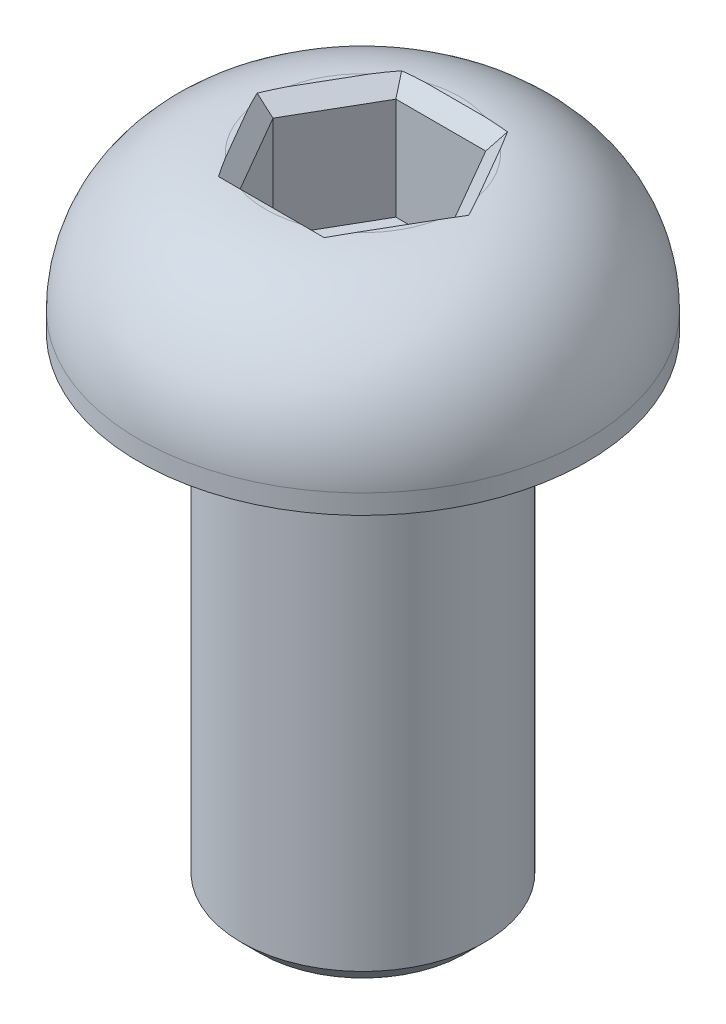
SolidWorks part; units mm, degrees
material "AISI 304"
ref_plane "Front Plane" through (0, 0, 0) normal (0, 0, 1) x (1, 0, 0)
ref_plane "Top Plane" through (0, 0, 0) normal (0, 1, 0) x (1, 0, 0)
ref_plane "Right Plane" through (0, 0, 0) normal (1, 0, 0) x (0, 0, -1)
sketch "Sketch1" plane through (0, 0, 0) normal (0, 0, 1) x (1, 0, 0)
  line L0 (0, 16.7549) -> (-2.54, 16.7549)
  line L1 (-5.842, 13.208) -> (-5.842, 12.7)
  line L2 (-5.842, 12.7) -> (-3.175, 12.7)
  line L3 (-3.175, 12.7) -> (-3.175, 0)
  line L4 (0, 16.7549) -> (0, 0)
  line L5 (-3.175, 0) -> (0, 0)
  line L16 (0, 0) -> (0, 19.0681) construction
  arc A0 (-2.54, 16.7549) -> (-5.842, 13.208) centre (-2.286, 13.208) ccw
  dimension "D1" = 3.556
  dimension "D2" = 4.572
  dimension "D3" = 0.508
  dimension "D4" = 0.508
  dimension "D5" = 11.684
  dimension "D6" = 6.35
  dimension "D7" = 16.7549
  dimension "D8" = 2.54
revolve "Revolve1" add sketch "Sketch1" angle 360 about L16
sketch "Sketch2" plane through (0, 16.7549, 0) normal (0, 1, 0) x (1, 0, 0)
  line L0 (0, 0) -> (3.0039, 0) construction
  line L1 (1.1732, -2.032) -> (2.3464, 0)
  line L2 (2.3464, 0) -> (1.1732, 2.032)
  line L3 (1.1732, 2.032) -> (-1.1732, 2.032)
  line L4 (-1.1732, 2.032) -> (-2.3464, 0)
  line L5 (-2.3464, 0) -> (-1.1732, -2.032)
  line L6 (-1.1732, -2.032) -> (1.1732, -2.032)
  circle A0 centre (0, 0) radius 2.032 construction
  dimension "D1" = 4.064
extrude "Extrude1" cut sketch "Sketch2" against normal blind 3.0477
chamfer "Chamfer1" distance 0.381 angle 45 3 edges at (1.7598, 16.7549, -1.016) (0, 16.7549, -2.032) (-1.7598, 16.7549, -1.016)
chamfer "Chamfer2" distance 0.381 angle 45 3 edges at (1.8475, 16.7549, 0.8641) (0, 16.7549, 2.032) (-1.8475, 16.7549, 0.8641)
chamfer "Chamfer3" distance 0.508 angle 45 1 edges at (0, 0, -3.175)
